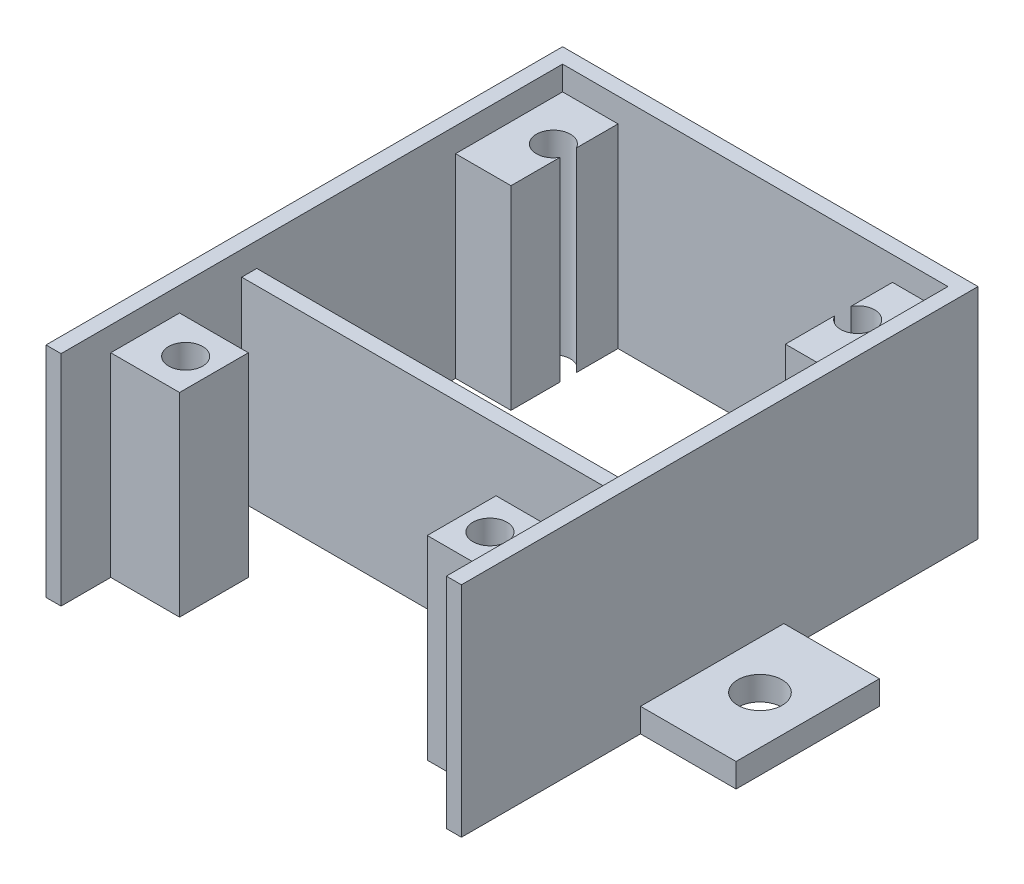
SolidWorks part; units mm, degrees
ref_plane "Front Plane" through (0, 0, 0) normal (0, 0, 1) x (1, 0, 0)
ref_plane "Top Plane" through (0, 0, 0) normal (0, 1, 0) x (1, 0, 0)
ref_plane "Right Plane" through (0, 0, 0) normal (1, 0, 0) x (0, 0, -1)
sketch "Sketch1" plane through (0, 0, 0) normal (0, 1, 0) x (1, 0, 0)
  line L0 (-10.9278, 9.0337) -> (16.6754, 9.0337)
  line L1 (-9.9278, 8.0337) -> (15.6754, 8.0337)
  line L2 (-9.9278, 8.0337) -> (-9.9278, -25.2911)
  line L3 (-9.9278, -25.2911) -> (15.6754, -25.2911)
  line L4 (15.6754, 8.0337) -> (15.6754, -25.2911)
  line L5 (16.6754, 9.0337) -> (16.6754, -26.2911)
  line L6 (-10.9278, -26.2911) -> (16.6754, -26.2911)
  line L7 (-10.9278, 9.0337) -> (-10.9278, -26.2911)
  dimension "D1" = 25.6032
  dimension "D2" = 33.3248
  dimension "D3" = 1
extrude "mainCasing" add sketch "Sketch1" against normal blind 12.93
sketch "Sketch2" plane through (0, -12.93, 0) normal (0, -1, 0) x (1, 0, 0)
  line L0 (-10.9278, -9.0337) -> (-10.9278, 26.2911) construction
  line L1 (-10.9278, 13.3912) -> (-17.2778, 13.3912)
  line L2 (-10.9278, 13.3912) -> (-10.9278, 3.8662)
  line L3 (-10.9278, 3.8662) -> (-17.2778, 3.8662)
  line L4 (-17.2778, 13.3912) -> (-17.2778, 3.8662)
  line L5 (16.6754, 26.2911) -> (16.6754, -9.0337) construction
  line L6 (16.6754, 13.3912) -> (23.0254, 13.3912)
  line L7 (16.6754, 13.3912) -> (16.6754, 3.8662)
  line L8 (16.6754, 3.8662) -> (23.0254, 3.8662)
  line L9 (23.0254, 13.3912) -> (23.0254, 3.8662)
  line L10 (19.8504, 13.3912) -> (19.8504, 3.8662) construction
  line L11 (23.0254, 8.6287) -> (16.6754, 8.6287) construction
  line L12 (-17.2778, 8.6287) -> (-10.9278, 8.6287) construction
  line L13 (-14.1028, 13.3912) -> (-14.1028, 3.8662) construction
  circle A0 centre (19.8504, 8.6287) radius 1.4732
  circle A1 centre (-14.1028, 8.6287) radius 1.4732
  dimension "D7" = 2.9464
  dimension "D8" = 2.9464
  dimension "D1" = 9.525
  dimension "D2" = 6.35
  dimension "D3" = 6.35
  dimension "D4" = 9.525
  dimension "D5" = 11.8999
  dimension "D6" = 11.8999
extrude "mountingTabs" add sketch "Sketch2" against normal blind 1.5875
sketch "Sketch3" plane through (0, 0, 0) normal (0, 1, 0) x (1, 0, 0)
  line L0 (15.6754, 8.0337) -> (-9.9278, 8.0337) construction
  line L1 (-6.2448, 8.0337) -> (-9.9278, 8.0337)
  line L2 (-6.2448, 8.0337) -> (-6.2448, 0.9217)
  line L3 (-6.2448, 0.9217) -> (-9.9278, 0.9217)
  line L4 (-9.9278, 8.0337) -> (-9.9278, 0.9217)
  line L5 (-9.9278, 8.0337) -> (-9.9278, -25.2911) construction
  line L6 (15.6754, -25.2911) -> (15.6754, 8.0337) construction
  line L7 (11.9924, 8.0337) -> (15.6754, 8.0337)
  line L8 (11.9924, 8.0337) -> (11.9924, 0.9217)
  line L9 (11.9924, 0.9217) -> (15.6754, 0.9217)
  line L10 (15.6754, 8.0337) -> (15.6754, 0.9217)
  line L11 (2.8738, 8.0337) -> (2.8738, -25.2911) construction
  line L12 (-9.9278, -25.2911) -> (15.6754, -25.2911) construction
  line L13 (-9.9278, -17.4171) -> (-5.3558, -17.4171)
  line L14 (-9.9278, -17.4171) -> (-9.9278, -21.9891)
  line L15 (-9.9278, -21.9891) -> (-5.3558, -21.9891)
  line L16 (-5.3558, -17.4171) -> (-5.3558, -21.9891)
  line L17 (15.6754, -17.4171) -> (11.1034, -17.4171)
  line L18 (15.6754, -17.4171) -> (15.6754, -21.9891)
  line L19 (15.6754, -21.9891) -> (11.1034, -21.9891)
  line L20 (11.1034, -17.4171) -> (11.1034, -21.9891)
  line L21 (-9.9278, -19.7031) -> (-5.3558, -19.7031) construction
  line L22 (11.1034, -19.7031) -> (15.6754, -19.7031) construction
  circle A0 centre (-7.2354, -19.7031) radius 1.1303
  circle A1 centre (12.983, -19.7031) radius 1.1303
  dimension "D13" = 2.2606
  dimension "D14" = 2.2606
  dimension "D1" = 4.572
  dimension "D2" = 4.572
  dimension "D3" = 7.112
  dimension "D4" = 3.683
  dimension "D5" = 7.112
  dimension "D6" = 3.683
  dimension "D7" = 4.572
  dimension "D8" = 4.572
  dimension "D9" = 18.3388
  dimension "D10" = 18.3388
  dimension "D11" = 10.1092
  dimension "D12" = 10.1092
extrude "Boss-Extrude3" add sketch "Sketch3" against normal blind 12.93
sketch "Sketch4" plane through (0, 0, 0) normal (0, 1, 0) x (1, 0, 0)
  line L0 (-10.9278, -26.2911) -> (-10.9278, 9.0337)
  line L1 (-9.9278, -25.2911) -> (15.6754, -25.2911)
  line L2 (-9.9278, -25.2911) -> (-9.9278, 8.0337)
  line L3 (-9.9278, 8.0337) -> (15.6754, 8.0337)
  line L4 (15.6754, -25.2911) -> (15.6754, 8.0337)
  line L5 (-10.9278, 9.0337) -> (16.6754, 9.0337)
  line L6 (16.6754, -26.2911) -> (16.6754, 9.0337)
  line L7 (-10.9278, -26.2911) -> (16.6754, -26.2911)
  dimension "D1" = 1
extrude "Boss-Extrude4" add sketch "Sketch4" along normal blind 1.6002
sketch "Sketch5" plane through (0, -12.93, 0) normal (0, -1, 0) x (1, 0, 0)
  line L0 (2.8738, 25.2911) -> (2.8738, -8.0337) construction
  line L1 (-9.9278, 25.2911) -> (15.6754, 25.2911) construction
  line L2 (11.9924, -8.0337) -> (-6.2448, -8.0337) construction
  circle A0 centre (-7.2354, -4.7317) radius 1.1303
  circle A1 centre (12.983, -4.7317) radius 1.1303
  dimension "D1" = 2.2606
  dimension "D2" = 2.2606
  dimension "D3" = 10.1092
  dimension "D4" = 10.1092
  dimension "D5" = 3.302
  dimension "D6" = 3.302
extrude "upperHoles" cut sketch "Sketch5" against normal through all
sketch "Sketch6" plane through (0, -12.93, 0) normal (0, -1, 0) x (1, 0, 0)
  line L0 (-9.9278, -0.9217) -> (-9.9278, 17.4171) construction
  line L1 (-9.9278, 13.2863) -> (15.6754, 13.2863)
  line L2 (-9.9278, 13.2863) -> (-9.9278, 12.2863)
  line L3 (-9.9278, 12.2863) -> (15.6754, 12.2863)
  line L4 (15.6754, 13.2863) -> (15.6754, 12.2863)
  line L5 (15.6754, 17.4171) -> (15.6754, -0.9217) construction
  dimension "D1" = 1
  dimension "D2" = 20.32
extrude "Boss-Extrude5" add sketch "Sketch6" against normal up to surface (12.93 mm away) up to face at (12.983, 0, 20.8334)
sketch "Sketch7" plane through (0, -12.93, 0) normal (0, -1, 0) x (1, 0, 0)
  line L0 (-10.9278, 13.3912) -> (-10.9278, 26.2911) construction
  line L1 (-10.9278, 26.2911) -> (16.6754, 26.2911)
  line L2 (-10.9278, 26.2911) -> (-10.9278, 25.2911)
  line L3 (-10.9278, 25.2911) -> (16.6754, 25.2911)
  line L4 (16.6754, 26.2911) -> (16.6754, 25.2911)
  line L5 (-10.9278, 26.2911) -> (16.6754, 26.2911) construction
  line L6 (16.6754, 26.2911) -> (16.6754, 13.3912) construction
extrude "Cut-Extrude2" cut sketch "Sketch7" against normal through all
